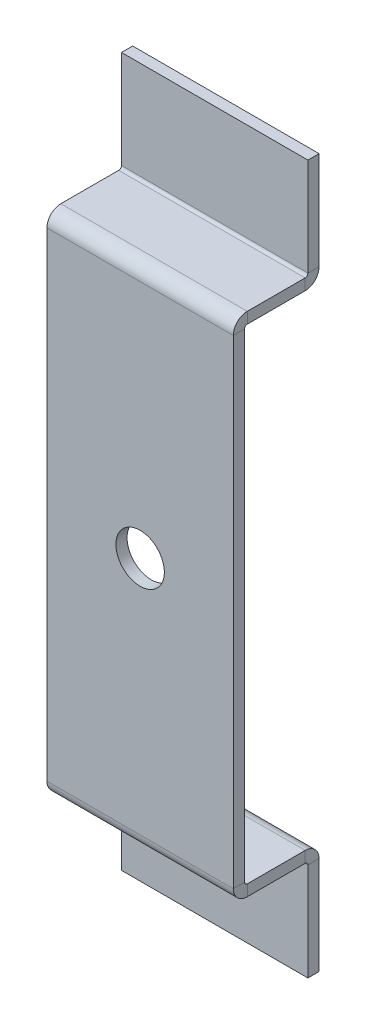
SolidWorks part; units mm, degrees
note: The reader was unsure of these and kept them because the rebuilt part matched: flange length of "边线-法兰1", "边线-法兰2".
ref_plane "前视基准面" through (0, 0, 0) normal (0, 0, 1) x (1, 0, 0)
ref_plane "上视基准面" through (0, 0, 0) normal (0, 1, 0) x (1, 0, 0)
ref_plane "右视基准面" through (0, 0, 0) normal (1, 0, 0) x (0, 0, -1)
other "Configuration Table"
sketch "草图1" plane through (0, 0, 0) normal (0, 0, 1) x (1, 0, 0)
  line L1 (0, 0) -> (50, 0)
  line L2 (0, 0) -> (0, 130)
  line L3 (0, 130) -> (50, 130)
  line L4 (50, 0) -> (50, 130)
  dimension "D1" = 130
  dimension "D2" = 50
base flange "基体-法兰1" sketch "草图1" thickness 3 reverse thickness direction no parameters "D1"=0.7366
edge flange "边线-法兰1" sketch "草图10" flange profiles "草图10", "草图11" flange angle 90 flange length 20 flange position material outside bend radius 0.7366 thickness 3 relief rectangular parameters "D6"=10, "D8"=1
sketch "草图10" plane through (0, 130, -3) normal (0, -1, 0) x (-1, 0, 0)
  line L2 (-50, 0) -> (-50, 17)
  line L3 (-50, 17) -> (0, 17)
  line L4 (0, 17) -> (0, 0)
  line L5 (0, 0) -> (-50, 0) construction
  line L6 (0, 0) -> (-50, 0)
sketch "草图11" plane through (0, 0, -3) normal (0, 1, 0) x (1, 0, 0)
  line L0 (50, 0) -> (0, 0) construction
  line L1 (50, 0) -> (0, 0)
  line L2 (50, 0) -> (50, 17)
  line L3 (50, 17) -> (0, 17)
  line L4 (0, 17) -> (0, 0)
bend "边线折弯1" bend radius 0.7366 bend angle 90 parameters "D5"=1
bend "边线折弯2" bend radius 0.7366 bend angle 90 parameters "D5"=2
edge flange "边线-法兰2" sketch "草图16" flange profiles "草图16", "草图17" flange angle 90 flange length 30 flange position material outside bend radius 0.7366 thickness 3 relief rectangular parameters "D6"=10, "D8"=1
sketch "草图16" plane through (0, -3, -20) normal (0, 0, -1) x (1, 0, 0)
  line L2 (0, 0) -> (0, 27)
  line L3 (0, 27) -> (50, 27)
  line L4 (50, 27) -> (50, 0)
  line L7 (50, 0) -> (0, 0) construction
  line L8 (50, 0) -> (0, 0)
sketch "草图17" plane through (0, 133, -20) normal (0, 0, -1) x (-1, 0, 0)
  line L0 (0, 0) -> (-50, 0) construction
  line L1 (0, 0) -> (-50, 0)
  line L2 (-50, 0) -> (-50, 27)
  line L3 (-50, 27) -> (0, 27)
  line L4 (0, 27) -> (0, 0)
bend "边线折弯3" bend radius 0.7366 bend angle 90 parameters "D5"=3
bend "边线折弯4" bend radius 0.7366 bend angle 90 parameters "D5"=4
sketch "草图18" plane through (0, 0, 0) normal (0, 0, 1) x (1, 0, 0)
  line L7 (50, -30) -> (0, -30) construction
  line L8 (50, 0.7366) -> (50, 129.2634) construction
  circle A0 centre (25, 65) radius 6.5
  dimension "D5" = 13
  dimension "D3" = 95
  dimension "D4" = 25
extrude "切除-拉伸1" cut sketch "草图18" against normal through all normal cut yes
sketch "折弯-线1" plane through (0, 0, 0) normal (0, 1, 0) x (1, 0, 0)
sketch "边界框1" plane through (0, 0, 0) normal (0, 1, 0) x (1, 0, 0)
sheet metal parameters "钣金6" thickness 3 parameters "D1"=0.7366
flat pattern "平板型式6" [suppressed]
sketch "折弯-线2" plane through (0, 0, 0) normal (0, 1, 0) x (1, 0, 0)
sketch "边界框2" [suppressed] plane through (0, 0, 0) normal (0, 1, 0) x (1, 0, 0)
sheet metal parameters "钣金7" thickness 3 parameters "D1"=0.7366
flat pattern "平板型式6" [suppressed]
sketch "折弯-线2" plane through (0, 0, 0) normal (0, 1, 0) x (1, 0, 0)
sketch "边界框2" [suppressed] plane through (0, 0, 0) normal (0, 1, 0) x (1, 0, 0)
bend of the flat pattern "展平-<边线折弯1>1"
bend of the flat pattern "展平-<边线折弯2>1"
sheet metal parameters "钣金8" thickness 3 parameters "D1"=0.7366
flat pattern "平板型式6" [suppressed]
sketch "折弯-线2" plane through (0, 0, 0) normal (0, 1, 0) x (1, 0, 0)
sketch "边界框2" [suppressed] plane through (0, 0, 0) normal (0, 1, 0) x (1, 0, 0)
bend of the flat pattern "展平-<边线折弯1>1"
bend of the flat pattern "展平-<边线折弯2>1"
bend of the flat pattern "展平-<边线折弯3>1"
bend of the flat pattern "展平-<边线折弯4>1"
sheet metal parameters "钣金9" thickness 3 parameters "D1"=0.7366
flat pattern "平板型式6" [suppressed]
sketch "折弯-线2" plane through (0, 0, 0) normal (0, 1, 0) x (1, 0, 0)
sketch "边界框2" [suppressed] plane through (0, 0, 0) normal (0, 1, 0) x (1, 0, 0)
bend of the flat pattern "展平-<边线折弯1>1"
bend of the flat pattern "展平-<边线折弯2>1"
bend of the flat pattern "展平-<边线折弯3>1"
bend of the flat pattern "展平-<边线折弯4>1"
